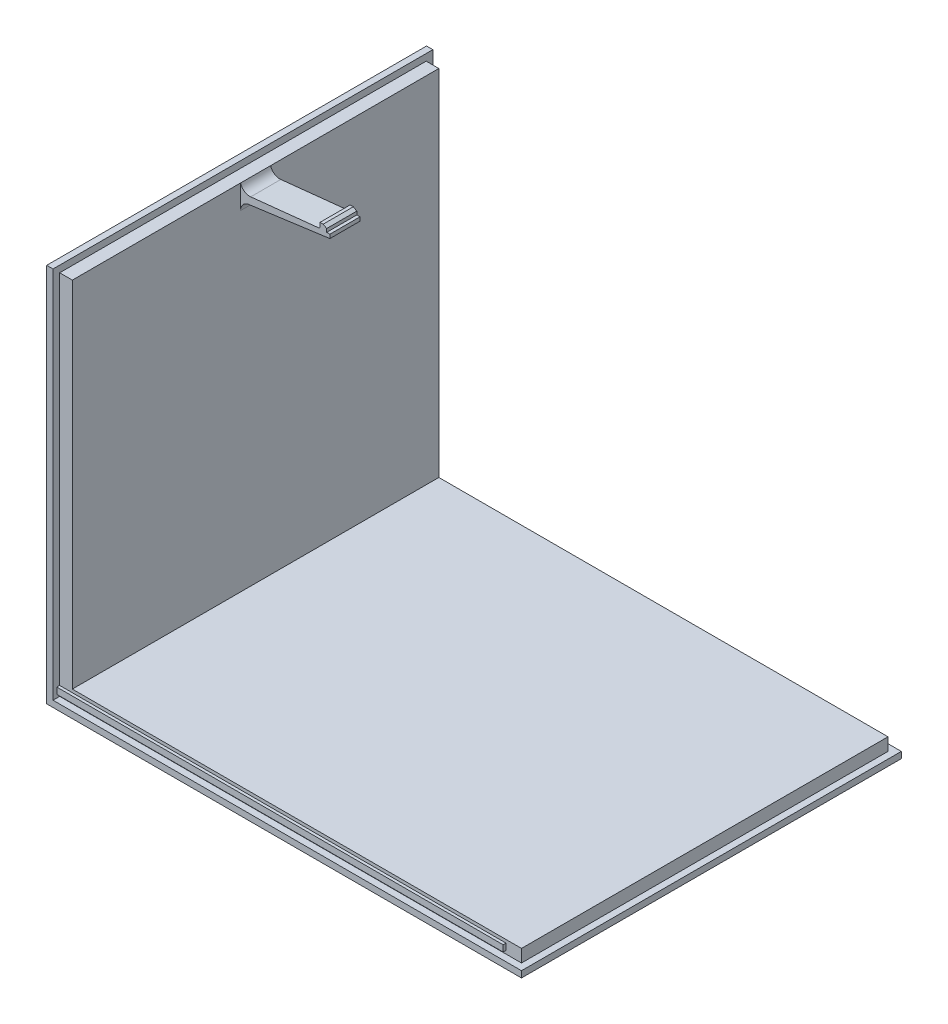
SolidWorks part; units mm, degrees
other "Markup1"
sketch "Sketch5" plane through (-105, 0, 60.5) normal (-0.0451, -0.9984, 0.0353) x (-0.7444, 0.01, -0.6676)
other "Markup2"
sketch "Sketch6" plane through (97, 11, -60) normal (0.0014, 0.7787, -0.6274) x (0.9996, 0.0165, 0.0227)
ref_plane "Front Plane" through (0, 0, 0) normal (0, 0, 1) x (1, 0, 0)
ref_plane "Top Plane" through (0, 0, 0) normal (0, 1, 0) x (1, 0, 0)
ref_plane "Right Plane" through (0, 0, 0) normal (1, 0, 0) x (0, 0, -1)
sketch "Sketch1" plane through (0, 0, 0) normal (0, 1, 0) x (1, 0, 0)
  line L1 (-75, 60) -> (75, 60)
  line L2 (-75, 60) -> (-75, -60)
  line L3 (-75, -60) -> (75, -60)
  line L4 (75, 60) -> (75, -60)
  point P4 (0, 60)
  point P5 (-75, 0)
  dimension "D1" = 120
  dimension "D2" = 150
extrude "Top" add sketch "Sketch1" along normal blind 2
sketch "Sketch2" plane through (0, 2, 0) normal (0, 1, 0) x (1, 0, 0)
  line L0 (-75, 60) -> (-75, -60) construction
  line L1 (-73, -57.9) -> (72.9, -57.9)
  line L2 (-73, -57.9) -> (-73, 57.9)
  line L3 (-73, 57.9) -> (72.9, 57.9)
  line L4 (72.9, -57.9) -> (72.9, 57.9)
  point P7 (72.9, 0)
  dimension "D1" = 115.8
  dimension "D2" = 2
  dimension "D3" = 145.9
extrude "Bottom" add sketch "Sketch2" along normal blind 4
sketch "Sketch8" plane through (0, 2, 0) normal (0, 1, 0) x (1, 0, 0)
  line L0 (-75, -60) -> (75, -60) construction
  line L1 (-75, 60) -> (-73, 60)
  line L2 (-75, 60) -> (-75, -60)
  line L3 (-75, -60) -> (-73, -60)
  line L4 (-73, 60) -> (-73, -60)
  dimension "D1" = 2
extrude "Boss-Extrude2" add sketch "Sketch8" along normal blind 118
sketch "Sketch10" plane through (-73, 0, 0) normal (1, 0, 0) x (0, 0, -1)
  line L1 (-57.9, 6) -> (57.9, 6)
  line L2 (-57.9, 6) -> (-57.9, 117.9)
  line L3 (-57.9, 117.9) -> (57.9, 117.9)
  line L4 (57.9, 6) -> (57.9, 117.9)
  point P4 (0, 117.9)
  dimension "D1" = 111.9
  dimension "D2" = 115.8
  dimension "D3" = 2.1
extrude "Boss-Extrude3" add sketch "Sketch10" along normal blind 4
sketch "Sketch11" plane through (-73, 0, 0) normal (1, 0, 0) x (0, 0, -1)
  line L0 (-57.9, 117.9) -> (-57.9, 2) construction
  line L1 (-57.9, 3) -> (-58.8, 3)
  line L2 (-57.9, 3) -> (-57.9, 5)
  line L3 (-57.9, 5) -> (-58.8, 5)
  line L4 (-58.8, 3) -> (-58.8, 5)
  line L6 (-57.9, 6) -> (-57.9, 2) construction
  line L7 (0, 0) -> (0, 41.6534) construction
  line L8 (58.8, 3) -> (58.8, 5)
  line L9 (57.9, 5) -> (58.8, 5)
  line L10 (57.9, 3) -> (57.9, 5)
  line L11 (57.9, 3) -> (58.8, 3)
  point P10 (-57.9, 4)
  point P11 (-57.9, 4)
  dimension "D1" = 2
  dimension "D2" = 0.9
extrude "Boss-Extrude4" add sketch "Sketch11" along normal blind 141
sketch "Sketch7" plane through (0, 0, 0) normal (0, 0, 1) x (1, 0, 0)
  line L1 (-69, 115.3724) -> (-69, 112.9724)
  line L17 (-69, 112.9724) -> (-40.7801, 116.8)
  line L18 (-41.7801, 119.06) -> (-42.8814, 119.6959)
  line L19 (-42.8814, 119.6959) -> (-43.8814, 119.6959)
  line L20 (-43.8814, 119.6959) -> (-44, 118)
  line L21 (-44, 118) -> (-69, 115.3724)
  line L22 (-41.7801, 118) -> (-41.7801, 119.06)
  line L23 (-41.7801, 118) -> (-40.7801, 118)
  line L24 (-40.7801, 118) -> (-40.7801, 116.8)
  line L25 (-73, 120) -> (-38.2157, 120) construction
  line L26 (-69, 118) -> (-37.8788, 118) construction
  point P55 (-7.5, 67.5)
extrude "Boss-Extrude1" add sketch "Sketch7" along normal mid plane 9.5
fillet "Fillet1" radius 3 2 edges at (-69, 115.3724, 0) (-69, 112.9724, 0)
